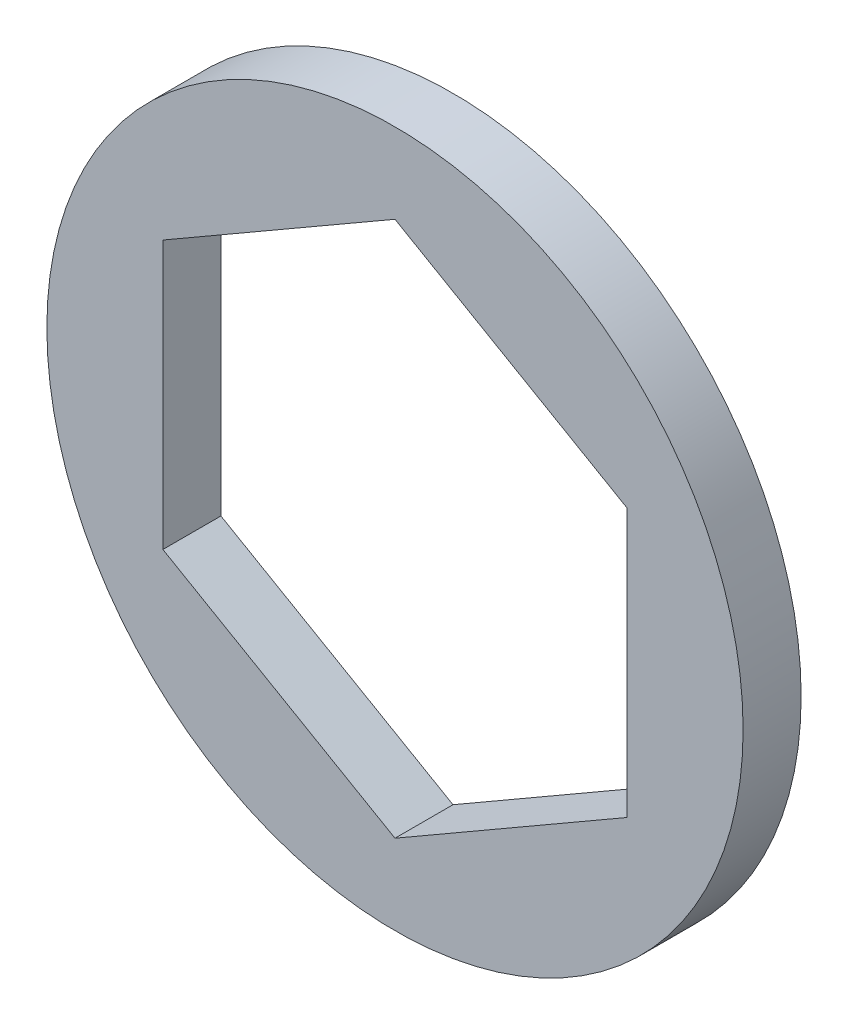
SolidWorks part; units mm, degrees
ref_plane "Front Plane" through (0, 0, 0) normal (0, 0, 1) x (1, 0, 0)
ref_plane "Top Plane" through (0, 0, 0) normal (0, 1, 0) x (1, 0, 0)
ref_plane "Right Plane" through (0, 0, 0) normal (1, 0, 0) x (0, 0, -1)
sketch "Sketch1" plane through (0, 0, 0) normal (0, 0, 1) x (1, 0, 0)
  line L1 (0, 7.3323) -> (-6.35, 3.6662)
  line L2 (-6.35, 3.6662) -> (-6.35, -3.6662)
  line L3 (-6.35, -3.6662) -> (0, -7.3323)
  line L4 (0, -7.3323) -> (6.35, -3.6662)
  line L5 (6.35, -3.6662) -> (6.35, 3.6662)
  line L6 (6.35, 3.6662) -> (0, 7.3323)
  circle A0 centre (0, 0) radius 9.525
  circle A1 centre (0, 0) radius 6.35 construction
  point P3 (0, 0)
  dimension "D1" = 19.05
  dimension "D2" = 12.7
extrude "Boss-Extrude1" add sketch "Sketch1" along normal blind 1.5875
